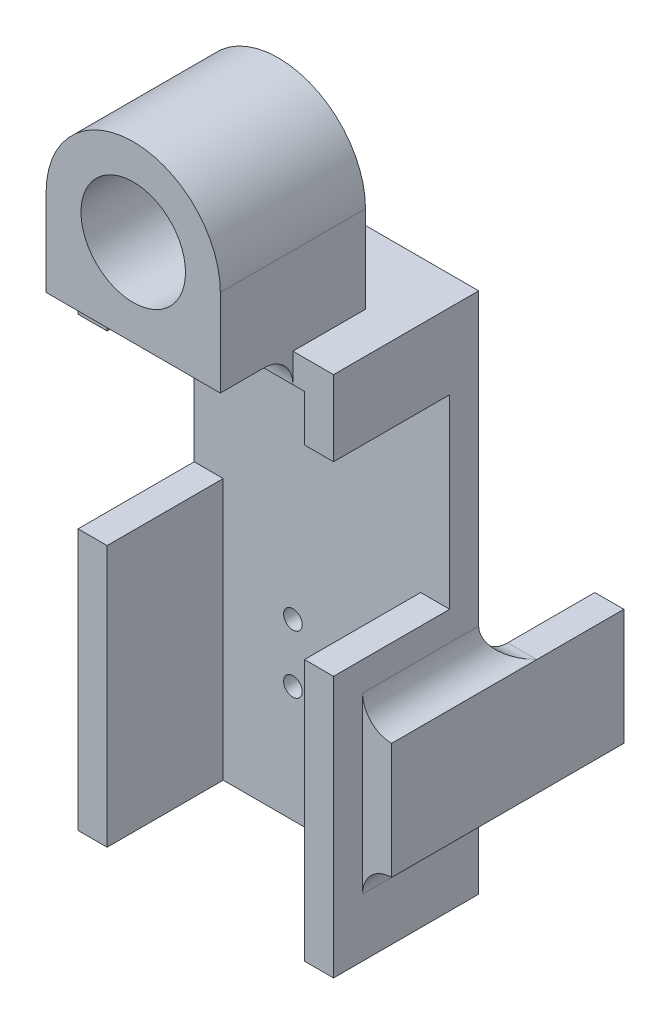
SolidWorks part; units mm, degrees
ref_plane "前视基准面" through (0, 0, 0) normal (0, 0, 1) x (1, 0, 0)
ref_plane "上视基准面" through (0, 0, 0) normal (0, 1, 0) x (1, 0, 0)
ref_plane "右视基准面" through (0, 0, 0) normal (1, 0, 0) x (0, 0, -1)
sketch "草图1" plane through (0, 0, 0) normal (0, 0, 1) x (1, 0, 0)
  line L1 (-22, 45) -> (22, 45)
  line L2 (-22, 45) -> (-22, -45)
  line L3 (-22, -45) -> (22, -45)
  line L4 (22, 45) -> (22, -45)
  line L5 (-22, 45) -> (22, -45) construction
  line L6 (-22, -45) -> (22, 45) construction
  point P0 (0, 0)
  dimension "D1" = 44
  dimension "D2" = 90
extrude "凸台-拉伸1" add sketch "草图1" along normal blind 25
sketch "草图2" plane through (0, 0, 25) normal (0, 0, 1) x (1, 0, 0)
  line L0 (22, 45) -> (-22, 45) construction
  line L1 (-17, 40) -> (17, 40)
  line L2 (-17, 40) -> (-17, -40)
  line L4 (17, 40) -> (17, -40)
  line L5 (-17, 40) -> (17, -40) construction
  line L6 (-17, -40) -> (17, 40) construction
  line L7 (22, -45) -> (22, 45) construction
  line L8 (-17, -40) -> (-17, -54.4667)
  line L9 (-17, -54.4667) -> (17, -54.4667)
  line L10 (17, -54.4667) -> (17, -40)
  line L11 (-22, 45) -> (-22, -45) construction
  point P0 (0, 0)
  dimension "D1" = 5
  dimension "D2" = 5
  dimension "D3" = 5
extrude "切除-拉伸1" cut sketch "草图2" against normal blind 20
sketch "草图3" plane through (0, 0, 0) normal (0, 0, -1) x (-1, 0, 0)
  line L0 (22, 45) -> (22, -45) construction
  line L1 (22, -10) -> (27, -10)
  line L2 (22, -10) -> (22, -30)
  line L3 (22, -30) -> (27, -30)
  line L4 (27, -10) -> (27, -30)
  line L5 (22, -45) -> (-22, -45) construction
  line L6 (0, 0) -> (0, -47.5467) construction
  line L7 (-27, -10) -> (-27, -30)
  line L8 (-22, -30) -> (-27, -30)
  line L9 (-22, -10) -> (-22, -30)
  line L10 (-22, -10) -> (-27, -10)
  dimension "D1" = 5
  dimension "D2" = 20
  dimension "D3" = 15
extrude "凸台-拉伸2" add sketch "草图3" along normal mid plane 40
fillet "圆角1" radius 5 4 edges at (22, -30, 10) (-22, -30, 10) (-22, -10, 10) (22, -10, 10)
fillet "圆角3" radius 5 4 edges at (-24.5, -30, 0) (24.5, -30, 0) (-24.5, -10, 0) (24.5, -10, 0)
sketch "草图4" plane through (0, 45, 0) normal (0, 1, 0) x (1, 0, 0)
  line L0 (22, -25) -> (-22, -25) construction
  line L1 (-15, -37.5) -> (15, -37.5)
  line L2 (-15, -37.5) -> (-15, -12.5)
  line L3 (-15, -12.5) -> (15, -12.5)
  line L4 (15, -37.5) -> (15, -12.5)
  line L5 (-15, -37.5) -> (15, -12.5) construction
  line L6 (-15, -12.5) -> (15, -37.5) construction
  point P0 (0, -25)
  dimension "D1" = 30
  dimension "D2" = 25
extrude "凸台-拉伸3" add sketch "草图4" along normal blind 15
sketch "草图5" plane through (0, 0, 37.5) normal (0, 0, 1) x (1, 0, 0)
  line L0 (-15, 60) -> (15, 60) construction
  circle A0 centre (0, 60) radius 15
  dimension "D1" = 30
extrude "凸台-拉伸4" add sketch "草图5" against normal blind 25
sketch "草图6" plane through (0, 0, 37.5) normal (0, 0, 1) x (1, 0, 0)
  circle A0 centre (0, 60) radius 9
  dimension "D1" = 18
extrude "切除-拉伸2" cut sketch "草图6" against normal blind 25
fillet "圆角4" radius 5 1 edges at (0, 45, 25)
sketch "草图7" plane through (0, 0, 25) normal (0, 0, 1) x (1, 0, 0)
  line L0 (17, 40) -> (-17, 40) construction
  line L1 (-38.1672, 32) -> (38.1672, 32)
  line L2 (-38.1672, 32) -> (-38.1672, 0)
  line L3 (-38.1672, 0) -> (38.1672, 0)
  line L4 (38.1672, 32) -> (38.1672, 0)
  line L5 (-38.1672, 32) -> (38.1672, 0) construction
  line L6 (-38.1672, 0) -> (38.1672, 32) construction
  point P0 (0, 16)
  dimension "D1" = 32
  dimension "D2" = 8
extrude "切除-拉伸3" cut sketch "草图7" against normal up to surface (20 mm away) up to face at (0, -2.5, 5)
sketch "草图9" plane through (0, 0, -20) normal (0, 0, -1) x (-1, 0, 0)
  line L0 (22, -5) -> (22, -35) construction
  line L1 (17, 10) -> (27, 10)
  line L2 (17, 10) -> (17, -30)
  line L3 (17, -30) -> (27, -30)
  line L4 (27, 10) -> (27, -30)
  line L5 (17, 10) -> (27, -30) construction
  line L6 (17, -30) -> (27, 10) construction
  line L7 (22, -10) -> (22, -30) construction
  point P0 (22, -10)
extrude "切除-拉伸5" cut sketch "草图9" against normal blind 5
sketch "草图10" plane through (0, 0, 0) normal (0, 0, -1) x (-1, 0, 0)
  line L0 (0, 0) -> (0, -58.8325) construction
  line L1 (-22, -20) -> (36.3404, -20) construction
  line L2 (-22, -35) -> (-22, -5) construction
  line L4 (-5, -15) -> (5, -15) construction
  line L5 (-5, -15) -> (-5, -25) construction
  line L6 (-5, -25) -> (5, -25) construction
  line L7 (5, -15) -> (5, -25) construction
  line L8 (-5, -15) -> (5, -25) construction
  line L9 (-5, -25) -> (5, -15) construction
  circle A0 centre (5, -15) radius 1.6
  circle A1 centre (5, -25) radius 1.6
  circle A2 centre (-5, -25) radius 1.6
  circle A3 centre (-5, -15) radius 1.6
  point P7 (0, -20)
  dimension "D3" = 3.2
  dimension "D4" = 3.2
  dimension "D5" = 3.2
  dimension "D6" = 3.2
  dimension "D1" = 10
  dimension "D2" = 10
extrude "切除-拉伸6" cut sketch "草图10" against normal blind 5
